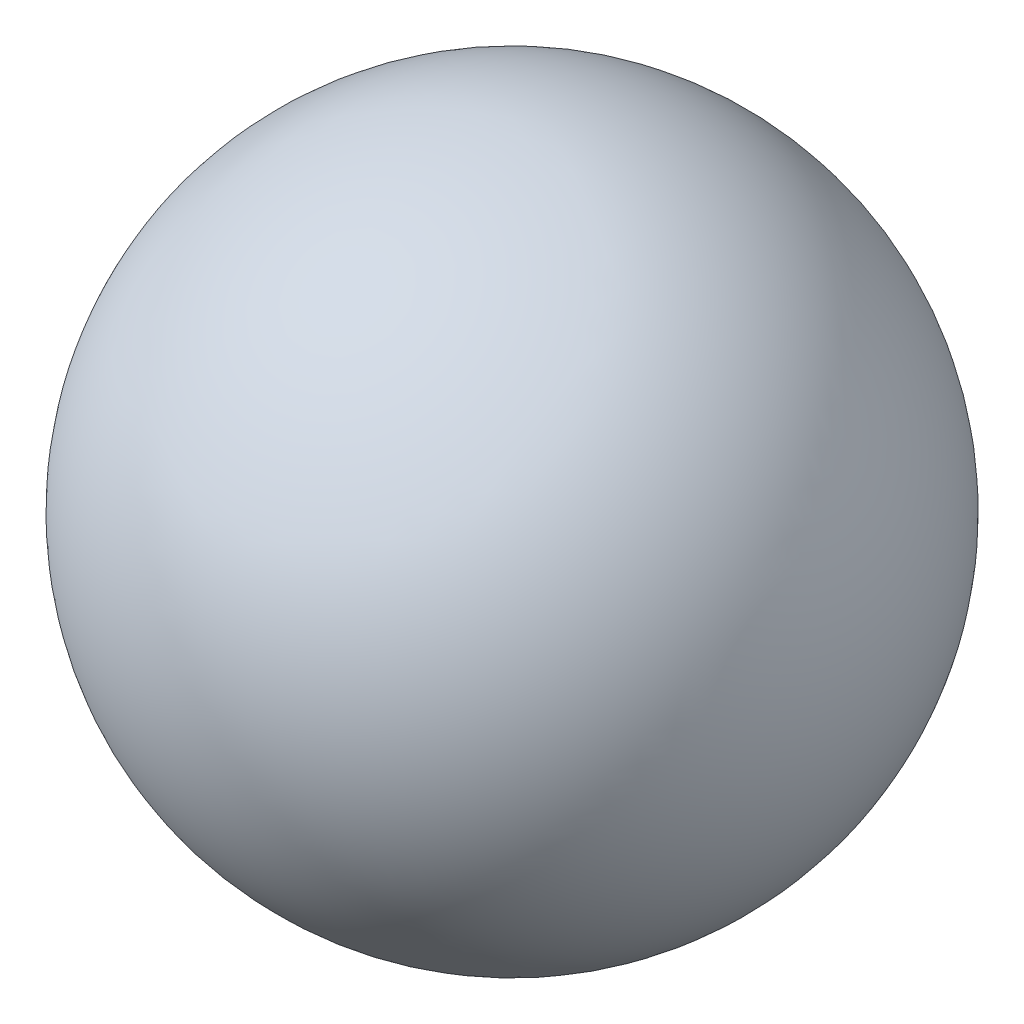
SolidWorks part; units mm, degrees
ref_plane "Front Plane" through (0, 0, 0) normal (0, 0, 1) x (1, 0, 0)
ref_plane "Top Plane" through (0, 0, 0) normal (0, 1, 0) x (1, 0, 0)
ref_plane "Right Plane" through (0, 0, 0) normal (1, 0, 0) x (0, 0, -1)
sketch "Sketch1" plane through (0, 0, 0) normal (0, 0, 1) x (1, 0, 0)
  line L0 (0.24, 0) -> (-0.24, 0)
  arc A0 (-0.24, 0) -> (0.24, 0) centre (0, 0) cw
  dimension "D1" = 0.24
revolve "Revolve1" add sketch "Sketch1" angle 360 about L0
